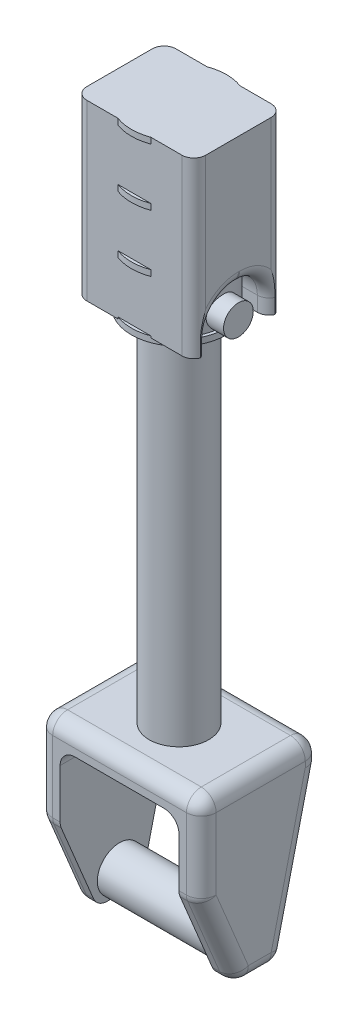
SolidWorks part; units mm, degrees
ref_plane "Front" through (0, 0, 0) normal (0, 0, 1) x (1, 0, 0)
ref_plane "Top" through (0, 0, 0) normal (0, 1, 0) x (1, 0, 0)
ref_plane "Right" through (0, 0, 0) normal (1, 0, 0) x (0, 0, -1)
sketch "Sketch1" plane through (0, 0, 0) normal (0, 0, 1) x (1, 0, 0)
  line L0 (0, -279.4) -> (38.1, -279.4) construction
  line L1 (76.2, -279.4) -> (-76.2, -279.4) construction
  line L2 (76.2, -279.4) -> (76.2, 279.4) construction
  line L3 (76.2, 279.4) -> (-76.2, 279.4) construction
  line L4 (-76.2, -279.4) -> (-76.2, 279.4) construction
  line L5 (76.2, -279.4) -> (-76.2, 279.4) construction
  line L6 (76.2, 279.4) -> (-76.2, -279.4) construction
  line L7 (38.1, -279.4) -> (38.1, -76.2) construction
  line L8 (38.1, -76.2) -> (-38.1, -76.2) construction
  line L9 (-38.1, -76.2) -> (-38.1, -279.4) construction
  line L10 (-38.1, -196.85) -> (-38.1, -158.75) construction
  line L11 (-50.8, -196.85) -> (-69.85, -196.85)
  line L12 (-69.85, -196.85) -> (-69.85, -44.45)
  line L13 (-69.85, -44.45) -> (69.85, -44.45)
  line L14 (69.85, -44.45) -> (69.85, -196.85)
  line L15 (69.85, -196.85) -> (50.8, -196.85)
  line L16 (50.8, -196.85) -> (50.8, -63.5)
  line L17 (50.8, -63.5) -> (-50.8, -63.5)
  line L18 (-50.8, -63.5) -> (-50.8, -196.85)
  point P0 (0, 0)
  dimension "D1" = 558.8
  dimension "D2" = 152.4
  dimension "D3" = 76.2
  dimension "D4" = 203.2
  dimension "D5" = 38.1
  dimension "D6" = 38.1
  dimension "D7" = 19.05
  dimension "D8" = 19.05
  dimension "D9" = 19.05
  dimension "D10" = 12.7
  dimension "D11" = 12.7
  dimension "D12" = 12.7
  dimension "D13" = 82.55
  dimension "D14" = 82.55
extrude "Boss-Extrude1" add sketch "Sketch1" against normal blind 101.6
sketch "Sketch2" plane through (69.85, 0, 0) normal (1, 0, 0) x (0, 0, -1)
  line L0 (101.6, -196.85) -> (0, -196.85) construction
  line L1 (0, -196.85) -> (0, -44.45) construction
  circle A0 centre (50.8, -177.8) radius 19.05
  dimension "D1" = 38.1
  dimension "D2" = 19.05
  dimension "D3" = 50.8
extrude "Boss-Extrude2" add sketch "Sketch2" against normal up to surface (120.65 mm away) up to face at (-50.8, -130.175, -50.8)
sketch "Sketch4" plane through (69.85, 0, 0) normal (1, 0, 0) x (0, 0, -1)
  line L0 (31.75, -196.85) -> (69.85, -196.85)
  line L1 (101.6, -196.85) -> (0, -196.85) construction
  line L3 (101.6, -196.85) -> (101.6, -44.45) construction
  line L4 (101.6, -63.5) -> (101.6, -196.85)
  line L5 (101.6, -196.85) -> (69.85, -196.85)
  line L6 (50.8, -44.45) -> (50.8, -233.0017) construction
  line L7 (101.6, -44.45) -> (0, -44.45) construction
  line L8 (69.85, -196.85) -> (101.6, -63.5)
  line L9 (31.75, -196.85) -> (0, -120.65)
  line L10 (0, -196.85) -> (0, -44.45) construction
  line L11 (0, -120.65) -> (0, -196.85)
  line L12 (0, -196.85) -> (31.75, -196.85)
  line M6 (0, -44.45) -> (0, -196.85)
  line M7 (0, -196.85) -> (101.6, -196.85)
  line M8 (101.6, -196.85) -> (101.6, -44.45)
  dimension "D1" = 38.1
  dimension "D2" = 31.75
  dimension "D3" = 19.05
extrude "Cut-Extrude1" cut sketch "Sketch4" against normal up to surface (139.7 mm away) contours L9 M7 M6 | L8 M7 M8 region at (69.85, -152.4, -91.0167) region at (69.85, -171.45, -10.5833) up to face at (-69.85, -120.65, -50.8)
fillet "Fillet1" radius 12.7 10 edges at (-50.8, -63.5, -50.8) (50.8, -63.5, -50.8) (0, -44.45, 0) (0, -44.45, -101.6) (60.325, -196.85, -31.75) (60.325, -196.85, -69.85) (-60.325, -196.85, -69.85) (-60.325, -196.85, -31.75) (-60.325, -120.65, 0) (60.325, -120.65, 0)
fillet "Fillet2" radius 12.7 22 edges at (-69.85, -120.6007, -0.2466) (-69.85, -156.0146, -14.7353) (-69.85, -194.717, -33.172) (-69.85, -196.85, -50.0177) (-69.85, -194.1161, -67.6906) (-69.85, -125.2958, -86.8867) (-69.85, -60.325, -101.6) (-69.85, -48.1697, -97.8803) (-69.85, -44.45, -50.8) (-69.85, -48.1697, -3.7197) (-69.85, -87.63, 0) (69.85, -48.1697, -97.8803) (69.85, -60.325, -101.6) (69.85, -125.2958, -86.8867) (69.85, -194.1161, -67.6906) (69.85, -196.85, -50.0177) (69.85, -194.717, -33.172) (69.85, -156.0146, -14.7353) (69.85, -120.6007, -0.2466) (69.85, -87.63, 0) (69.85, -48.1697, -3.7197) (69.85, -44.45, -50.8)
sketch "Sketch5" plane through (0, -44.45, 0) normal (0, 1, 0) x (1, 0, 0)
  circle A0 centre (0, 50.8) radius 25.4
  dimension "D1" = 50.8
extrude "Boss-Extrude3" add sketch "Sketch5" along normal blind 307.34
sketch "Sketch6" plane through (0, 262.89, 0) normal (0, 1, 0) x (1, 0, 0)
  circle A0 centre (0, 50.8) radius 40.64
  dimension "D1" = 81.28
extrude "Boss-Extrude4" add sketch "Sketch6" along normal blind 5.08
sketch "Sketch7" plane through (0, 267.97, 0) normal (0, 1, 0) x (1, 0, 0)
  circle A0 centre (0, 50.8) radius 38.1
  dimension "D1" = 76.2
extrude "Boss-Extrude5" add sketch "Sketch7" along normal blind 43.942
fillet "Fillet5" radius 7.62 1 edges at (0, 311.912, -12.7)
sketch "Sketch8" plane through (0, 311.912, 0) normal (0, 1, 0) x (1, 0, 0)
  circle A0 centre (0, 50.8) radius 40.64
  dimension "D1" = 81.28
extrude "Boss-Extrude6" add sketch "Sketch8" along normal blind 5.08
sketch "Sketch9" plane through (0, 316.992, 0) normal (0, 1, 0) x (1, 0, 0)
  circle A0 centre (0, 50.8) radius 38.1
  dimension "D1" = 76.2
extrude "Boss-Extrude7" add sketch "Sketch9" along normal blind 43.942
fillet "Fillet6" radius 7.62 1 edges at (0, 360.934, -12.7)
sketch "Sketch10" plane through (0, 360.934, 0) normal (0, 1, 0) x (1, 0, 0)
  circle A0 centre (0, 50.8) radius 40.64
  dimension "D1" = 81.28
extrude "Boss-Extrude8" add sketch "Sketch10" along normal blind 5.08
sketch "Sketch11" plane through (0, 366.014, 0) normal (0, 1, 0) x (1, 0, 0)
  circle A0 centre (0, 50.8) radius 38.1
  dimension "D1" = 76.2
extrude "Boss-Extrude9" add sketch "Sketch11" along normal blind 43.942
fillet "Fillet7" radius 7.62 1 edges at (0, 409.956, -12.7)
sketch "Sketch12" plane through (0, 409.956, 0) normal (0, 1, 0) x (1, 0, 0)
  circle A0 centre (0, 50.8) radius 40.64
  dimension "D1" = 81.28
extrude "Boss-Extrude10" add sketch "Sketch12" along normal blind 5.08
sketch "Sketch13" plane through (0, 0, 0) normal (1, 0, 0) x (0, 0, -1)
  line L0 (50.8, 415.036) -> (12.7, 415.036)
  line L1 (91.44, 415.036) -> (10.16, 415.036) construction
  line L2 (12.7, 415.036) -> (12.7, 266.446)
  line L3 (12.7, 266.446) -> (25.4, 266.446)
  line L4 (25.4, 266.446) -> (25.4, 279.146)
  line L5 (50.8, 304.546) -> (51.7783, 304.546)
  line L6 (77.1783, 279.146) -> (77.1783, 266.446)
  line L7 (77.1783, 266.446) -> (88.9, 266.446)
  line L8 (88.9, 266.446) -> (88.9, 415.036)
  line L9 (88.9, 415.036) -> (50.8, 415.036)
  line L10 (50.8, 415.036) -> (50.8, 279.146) construction
  circle A0 centre (50.8, 279.146) radius 12.7
  arc A1 (50.8, 304.546) -> (25.4, 279.146) centre (50.8, 279.146) ccw
  arc A2 (77.1783, 279.146) -> (51.7783, 304.546) centre (51.7783, 279.146) ccw
  point P15 (25.4, 304.546)
extrude "Boss-Extrude11" add sketch "Sketch13" along normal blind 50.8 and the other way blind 50.8
fillet "Fillet3" radius 10.16 4 edges at (50.8, 340.741, -12.7) (-50.8, 340.741, -12.7) (-50.8, 340.741, -88.9) (50.8, 340.741, -88.9)
fillet "Fillet4" radius 10.16 10 edges at (-50.8, 272.796, -77.1783) (-50.8, 272.796, -25.4) (-50.8, 297.1065, -32.8395) (-50.8, 304.546, -51.2891) (50.8, 272.796, -77.1783) (50.8, 297.1065, -69.7388) (50.8, 304.546, -51.2891) (50.8, 272.796, -25.4) (-50.8, 297.1065, -69.7388) (50.8, 297.1065, -32.8395)
